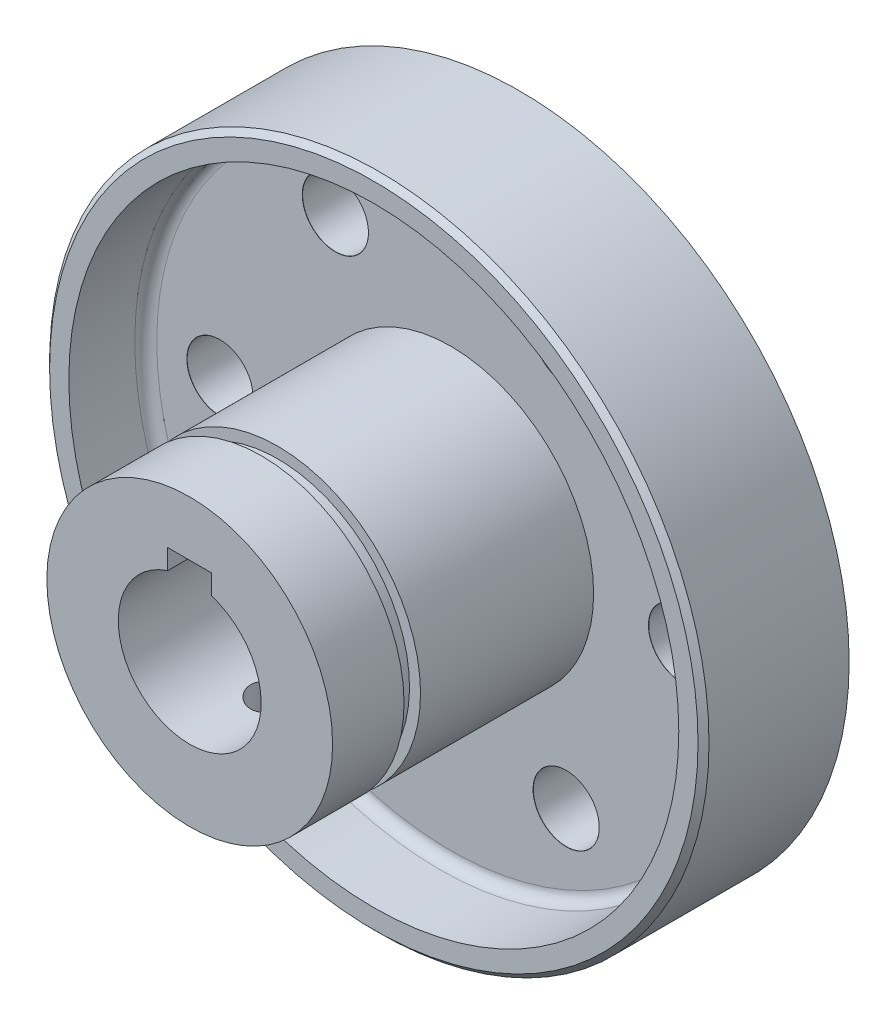
SolidWorks part; units mm, degrees
ref_plane "前视基准面" through (0, 0, 0) normal (0, 0, 1) x (1, 0, 0)
ref_plane "上视基准面" through (0, 0, 0) normal (0, 1, 0) x (1, 0, 0)
ref_plane "右视基准面" through (0, 0, 0) normal (1, 0, 0) x (0, 0, -1)
sketch "草图1" plane through (0, 0, 0) normal (0, 0, 1) x (1, 0, 0)
  circle A0 centre (0, 0) radius 60
  dimension "D1" = 120
extrude "凸台-拉伸1" add sketch "草图1" along normal blind 26.5
sketch "草图2" plane through (0, 0, 0) normal (0, 0, 1) x (1, 0, 0)
  circle A0 centre (0, 0) radius 26
  dimension "D1" = 52
extrude "凸台-拉伸2" add sketch "草图2" along normal blind 60
sketch "草图3" plane through (0, 0, 26.5) normal (0, 0, 1) x (1, 0, 0)
  circle A0 centre (0, 0) radius 55.5
  circle A2 centre (0, 0) radius 26
  circle A3 centre (0, 0) radius 26
  dimension "D1" = 111
  dimension "D2" = 0
extrude "切除-拉伸1" cut sketch "草图3" against normal blind 14
sketch "草图4" plane through (0, 0, 60) normal (0, 0, 1) x (1, 0, 0)
  line L0 (0, 13) -> (4, 10) construction
  line L1 (-4, 10) -> (4, 10) construction
  line L2 (-4, 12.3693) -> (-4, 16)
  line L3 (-4, 16) -> (4, 16)
  line L4 (4, 12.3693) -> (4, 16)
  line L5 (0, 13) -> (4, 16) construction
  line L6 (-4, 16) -> (0, 13) construction
  line L7 (4, 10) -> (4, 12.3693) construction
  line L8 (-4, 10) -> (0, 13) construction
  line L9 (-4, 10) -> (-4, 12.3693) construction
  arc A0 (-4, 12.3693) -> (4, 12.3693) centre (0, 0) ccw
  arc A1 (0, 13) -> (-4, 12.3693) centre (0, 0) ccw construction
  arc A2 (4, 12.3693) -> (0, 13) centre (0, 0) ccw construction
  point P3 (0, 13)
  dimension "D1" = 26
  dimension "D3" = 29
  dimension "D2" = 8
extrude "切除-拉伸2" cut sketch "草图4" against normal through all
sketch "草图5" plane through (0, 0, 60) normal (0, 0, 1) x (1, 0, 0)
  circle A2 centre (0, 0) radius 24
  circle A3 centre (0, 0) radius 24
  circle A4 centre (0, 0) radius 26
  circle A5 centre (0, 0) radius 26
  dimension "D1" = 2
  dimension "D2" = 0
hole_wizard "M8 螺纹孔的螺纹孔钻头1" positions "3D草图1" profile "草图6" hole size "M8" standard "GB" end condition up to next
sketch3d "3D草图1"
  point P0 (0, -26, 45.5)
  point P4 (0, 0, 0)
  dimension "D1" = 14.5
sketch "草图6" plane through (0, -26, 45.5) normal (1, 0, 0) x (0, 0, -1)
  line L0 (0, 0) -> (0, 13)
  line L1 (0, 13) -> (3.4, 13)
  line L2 (3.4, 13) -> (3.4, 0.025)
  line L3 (3.4, 0.025) -> (3.425, 0)
  line L5 (3.425, 0) -> (0, 0)
  line L6 (-3.4, 0.025) -> (-3.425, 0) construction
  line L11 (0, -6.35) -> (0, 107.95) construction
  dimension "通孔孔直径" = 6.8
  dimension "通孔孔深度" = 13
  dimension "近端锥形沉头孔直径" = 6.85
  dimension "近端锥形沉头孔角度" = 90
extrude "切除-拉伸3" cut sketch "草图5" against normal blind 3 from offset 13 offset against normal yes
sketch "草图7" plane through (0, 0, 12.5) normal (0, 0, 1) x (1, 0, 0)
  circle A0 centre (0, 0) radius 42 construction
  point P3 (42, 0)
  point P7 (21, -36.3731)
  point P8 (-21, -36.3731)
  point P9 (-42, 0)
  point P10 (-21, 36.3731)
  point P11 (21, 36.3731)
  dimension "D1" = 84
  dimension "D2" = 6
hole_wizard "Ø12.0 (12) 直径孔1" positions "草图7" profile "草图8" hole size "Ø12.0" standard "GB" end condition up to next
sketch "草图8" plane through (21, 36.3731, 12.5) normal (1, 0, 0) x (0, -1, 0)
  line L0 (0, 0) -> (0, 12.5)
  line L1 (0, 12.5) -> (6, 12.5)
  line L2 (6, 12.5) -> (6, 0.025)
  line L3 (6, 0.025) -> (6.025, 0)
  line L5 (6.025, 0) -> (0, 0)
  line L6 (-6, 0.025) -> (-6.025, 0) construction
  line L11 (0, -6.35) -> (0, 107.95) construction
  dimension "通孔孔直径" = 12
  dimension "通孔孔深度" = 12.5
  dimension "近端锥形沉头孔直径" = 12.05
  dimension "近端锥形沉头孔角度" = 90
chamfer "倒角1" distance 1 angle 45 1 edges at (60, 0, 26.5)
fillet "圆角1" radius 2 1 edges at (55.5, 0, 12.5)
